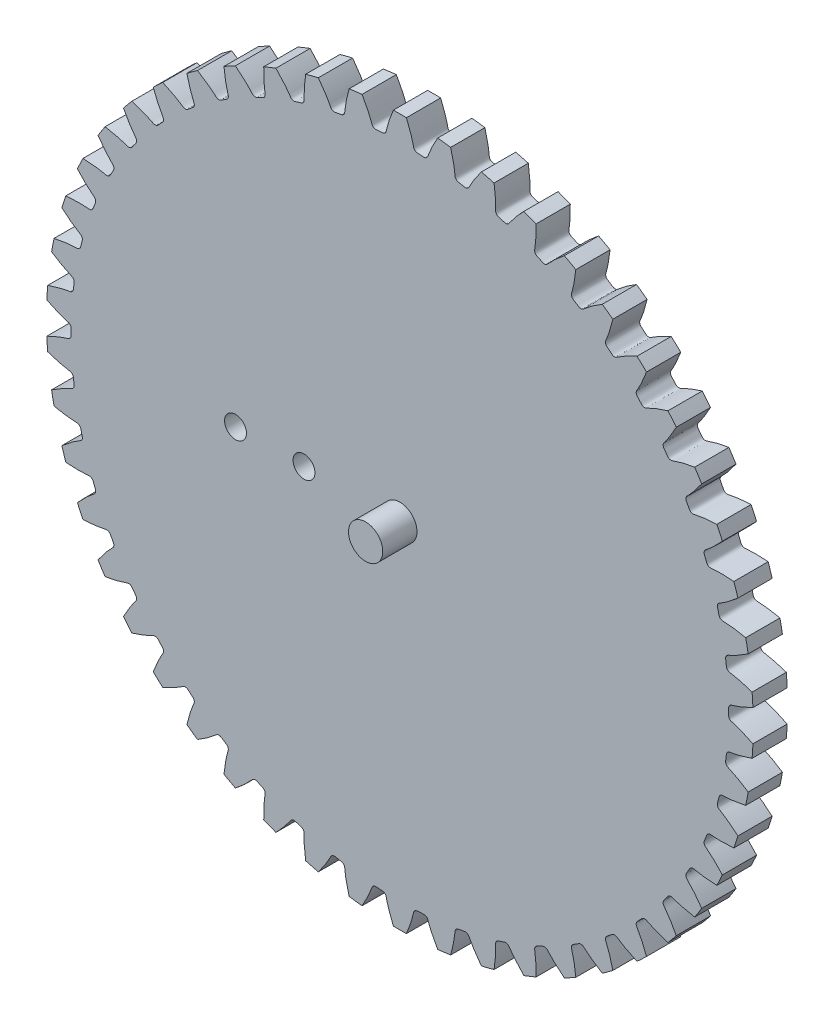
SolidWorks part; units mm, degrees
ref_plane "前视基准面" through (0, 0, 0) normal (0, 0, 1) x (1, 0, 0)
ref_plane "上视基准面" through (0, 0, 0) normal (0, 1, 0) x (1, 0, 0)
ref_plane "右视基准面" through (0, 0, 0) normal (1, 0, 0) x (0, 0, -1)
other "Configuration Table"
ref_axis "基准轴1" through (0, 0, 55) along (0, 0, -1)
sketch "SketchRevolveSpurGear2" plane through (0, 0, 0) normal (1, 0, 0) x (0, 0, -1)
  line L0 (0, 0) -> (1, 0) construction
  line L1 (-10, 0) -> (-10, 51.6)
  line L2 (-10, 51.6) -> (10, 51.6)
  line L3 (10, 51.6) -> (10, 0)
  line L4 (10, 0) -> (-10, 0)
revolve "SpurGear2" add sketch "SketchRevolveSpurGear2" angle 360 about L0
sketch "SketchToothSpurGear2" plane through (0, 0, 0) normal (0, 0, 1) x (1, 0, 0)
  arc A0 (51.6276, 2.327) -> (51.6276, -2.327) centre (0, 0) cw
  spline S0 degree 3 poles (51.6276, -2.327) (51.4367, -2.2289) (51.1832, -2.1034) (50.8669, -1.9551) (50.6853, -1.8722) (50.5074, -1.7932) (50.3334, -1.718) (50.1632, -1.6466) (49.9968, -1.5788) (49.8345, -1.5146) (49.6762, -1.4539) (49.5219, -1.3965) (49.3718, -1.3424) (49.2258, -1.2916) (49.0841, -1.2438) (48.9466, -1.1992) (48.727, -1.1293) (48.5197, -1.0753) (48.3316, -1.0064) (48.2488, -0.9563) (48.1748, -0.8944) (48.1117, -0.8213) (48.061, -0.7391) (48.0243, -0.6498) (48.0015, -0.5558) (47.995, -0.4149) (48.0009, -0.2298) (47.9995, 0) (48.0009, 0.2298) (47.995, 0.4149) (48.0015, 0.5558) (48.0243, 0.6498) (48.061, 0.7391) (48.1117, 0.8213) (48.1748, 0.8944) (48.2488, 0.9563) (48.3316, 1.0064) (48.5197, 1.0753) (48.727, 1.1293) (48.9466, 1.1992) (49.0841, 1.2438) (49.2258, 1.2916) (49.3718, 1.3424) (49.5219, 1.3965) (49.6762, 1.4539) (49.8345, 1.5146) (49.9968, 1.5788) (50.1632, 1.6466) (50.3334, 1.718) (50.5074, 1.7932) (50.6853, 1.8722) (50.8669, 1.9551) (51.1832, 2.1034) (51.4367, 2.2289) (51.6276, 2.327) knots 0 0 0 0 0.068658 0.090477 0.111762 0.132514 0.152732 0.172417 0.191568 0.210185 0.228269 0.245819 0.262835 0.279318 0.295268 0.310683 0.325565 0.368965 0.37922 0.389474 0.399729 0.409983 0.420237 0.430492 0.440746 0.451001 0.475501 0.5 0.524499 0.548999 0.559254 0.569508 0.579763 0.590017 0.600271 0.610526 0.62078 0.631035 0.674435 0.689317 0.704732 0.720682 0.737165 0.754181 0.771731 0.789815 0.808432 0.827583 0.847268 0.867486 0.888238 0.909523 0.931342 1 1 1 1
extrude "ToothExtrudeCutSpurGear2" cut sketch "SketchToothSpurGear2" against normal blind 10 and the other way blind 10
pattern_circular "PatternSpurGear2" count 50 every 7.2 about axis through (0, 0, 55) along (0, 0, -1) of "ToothExtrudeCutSpurGear2"
sketch "BoreRevolveSketch" plane through (0, 0, 0) normal (1, 0, 0) x (0, 0, -1)
  line L0 (0, 0) -> (1, 0) construction
  line L1 (-10, 0) -> (10, 0)
  line L2 (10, 0) -> (10, 5)
  line L3 (10, 5) -> (-10, 5)
  line L4 (-10, 5) -> (-10, 0)
  dimension "TaperSide1" = 5
  dimension "TaperSide2" = 5
revolve "BoreRevolveCut" cut sketch "BoreRevolveSketch" angle 360 about L0
sketch "AuxiliarySketchSpurGear2" plane through (0, 0, 0) normal (0, 0, 1) x (1, 0, 0)
  circle A0 centre (0, 0) radius 50 construction
  circle A1 centre (0, 0) radius 46.9846 construction
  circle A2 centre (0, 0) radius 48.5953 construction
  circle A3 centre (0, 0) radius 51.6 construction
  circle A4 centre (0, 0) radius 48 construction
  dimension "PitchDiameter" = 100
  dimension "BaseDiameter" = 93.9693
  dimension "FormDiameter" = 97.1907
  dimension "MajorDiameter" = 103.2
  dimension "MinorDiameter" = 96
sketch "草图5" plane through (0, 0, 10) normal (0, 0, 1) x (1, 0, 0)
  circle A0 centre (0, 0) radius 51.6
extrude "切除-拉伸2" cut sketch "草图5" against normal blind 15
sketch "草图6" plane through (0, 0, -5) normal (0, 0, 1) x (1, 0, 0)
  circle A0 centre (0, 0) radius 5
extrude "凸台-拉伸1" add sketch "草图6" against normal blind 5
sketch "草图7" plane through (0, 0, -10) normal (0, 0, -1) x (-1, 0, 0)
  line L0 (0, 0) -> (48, 0)
  circle A0 centre (0, 0) radius 48 construction
  circle A1 centre (24, 0) radius 1.6
  circle A2 centre (14, 0) radius 1.6
  dimension "D1" = 3.2
  dimension "D2" = 3.2
  dimension "D3" = 10
  dimension "D4" = 14
extrude "切除-拉伸6" cut sketch "草图7" against normal blind 5 contours L0 A2 | L0 A2 | L0 A1 | L0 A1 region at (-14, 0.6791, -10) region at (-24, 0.6791, -10) region at (-24, -0.6791, -10) region at (-14, -0.6791, -10)
sketch "草图8" plane through (0, 0, -5) normal (0, 0, 1) x (1, 0, 0)
  circle A0 centre (0, 0) radius 2.5
  dimension "D1" = 5
extrude "凸台-拉伸2" add sketch "草图8" along normal blind 5
